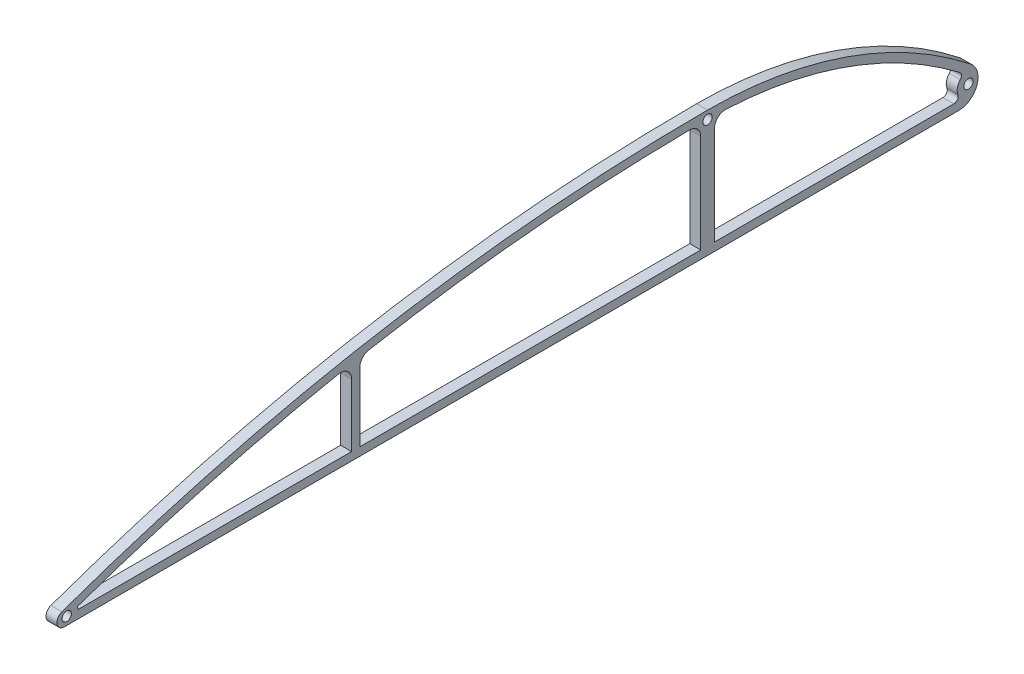
SolidWorks part; units mm, degrees
other "Marquage1"
sketch "Esquisse8" plane through (8, 0, -172.8424) normal (1, 0, 0) x (0, 0, -1)
other "Marquage2"
sketch "Esquisse10" plane through (-6, 20, -172.8424) normal (-0.8365, 0.2588, -0.483) x (-0.5, 0, 0.866)
other "Marquage3"
sketch "Esquisse11" plane through (0, 0, 0) normal (-0.0501, -0.1345, 0.9896) x (0.9942, 0.0873, 0.0622)
ref_plane "Plan de face" through (0, 0, 0) normal (0, 0, 1) x (1, 0, 0)
ref_plane "Plan de dessus" through (0, 0, 0) normal (0, 1, 0) x (1, 0, 0)
ref_plane "Plan de droite" through (0, 0, 0) normal (1, 0, 0) x (0, 0, -1)
sketch "Esquisse2" plane through (0, 0, 0) normal (1, 0, 0) x (0, 0, -1)
  line L0 (0, 0) -> (170.8732, 0)
  arc A1 (173.0499, 6.2408) -> (125, 23) centre (125, -54.2609) ccw
  arc A3 (170.8732, 0) -> (173.0499, 6.2408) centre (170.8732, 3.5) ccw
  arc A4 (125, 23) -> (0, 0) centre (125, -328.1739) ccw
  point P10 (180, 0)
  dimension "D1" = 180
  dimension "D2" = 3.5
  dimension "D3" = 23
  dimension "D4" = 55
extrude "Boss.-Extru.1" add sketch "Esquisse2" along normal blind 2
sketch "Esquisse4" plane through (2, 0, 0) normal (1, 0, 0) x (0, 0, -1)
  line L0 (8, 0) -> (8, 2.9365) construction
  line L1 (0, 0) -> (8, 1.4683) construction
  line L10 (174.369, 3.3283) -> (172.619, 3.3283) construction
  line L11 (0, 0) -> (170.8732, 0) construction
  circle A6 centre (125, 21.5) radius 0.85
  circle A12 centre (172.619, 3.3283) radius 0.85
  arc A13 (170.8732, 0) -> (173.0499, 6.2408) centre (170.8732, 3.5) ccw construction
  circle A15 centre (8, 1.4683) radius 0.85
  arc A16 (125, 23) -> (0, 0) centre (125, -328.1739) ccw construction
  dimension "D1" = 1.7
  dimension "D2" = 1.7
  dimension "D7" = 1.7
  dimension "D3" = 1.5
  dimension "D4" = 8
  dimension "D6" = 1.75
extrude "Enlèv. mat.-Extru.2" cut sketch "Esquisse4" against normal through all
sketch "Esquisse9" plane through (0, 0, 0) normal (1, 0, 0) x (0, 0, -1)
  line L26 (126.25, 1.5) -> (171.6918, 1.5)
  line L35 (8.4369, 1.5) -> (170.8732, 1.5)
  line L36 (10.0498, 1.5) -> (60, 1.5)
  line L40 (61.5, 1.5) -> (123.75, 1.5)
  line L42 (60, 1.5) -> (60, 15.4055)
  line L44 (61.5, 1.5) -> (61.5, 15.6859)
  line L45 (123.75, 21.4978) -> (123.75, 1.5)
  line L46 (126.25, 21.4978) -> (126.25, 1.5)
  arc A20 (60, 15.4055) -> (9.9693, 2.0378) centre (125, -328.1739) ccw
  circle A21 centre (125, 21.5) radius 0.85 construction
  circle A22 centre (8, 1.4683) radius 0.85 construction
  arc A23 (173.0499, 6.2408) -> (125, 23) centre (125, -54.2609) ccw construction
  arc A25 (171.9, 5.2481) -> (171.6918, 1.5) centre (172.619, 3.3283) ccw
  circle A26 centre (172.619, 3.3283) radius 0.85 construction
  arc A35 (170.8732, 1.5) -> (172.117, 5.0662) centre (170.8732, 3.5) ccw
  arc A39 (172.117, 5.0662) -> (125, 21.5) centre (125, -54.2609) ccw
  arc A40 (125, 21.5) -> (8.4369, 1.5) centre (125, -328.1739) ccw
  arc A42 (171.9, 5.2481) -> (126.25, 21.4978) centre (125, -54.2609) ccw
  arc A43 (123.75, 21.4978) -> (61.5, 15.6859) centre (125, -328.1739) ccw
  arc A54 (10.0498, 1.5) -> (9.9693, 2.0378) centre (8, 1.4683) ccw
  dimension "D1" = 1.5
  dimension "D2" = 1.25
  dimension "D3" = 1.2
  dimension "D5" = 1.25
  dimension "D4" = 1.2
  dimension "D6" = 1.5
  dimension "D7" = 60
extrude "Enlèv. mat.-Extru.3" cut sketch "Esquisse9" along normal blind 4
fillet "Congé2" radius 1.35 1 edges at (1, 0, 0)
fillet "Congé3" radius 2 4 edges at (1, 21.4978, -126.25) (1, 21.4978, -123.75) (1, 15.4055, -60) (1, 15.6859, -61.5)
fillet "Congé4" radius 0.8 2 edges at (1, 1.5, -171.6918) (1, 5.2481, -171.9)
